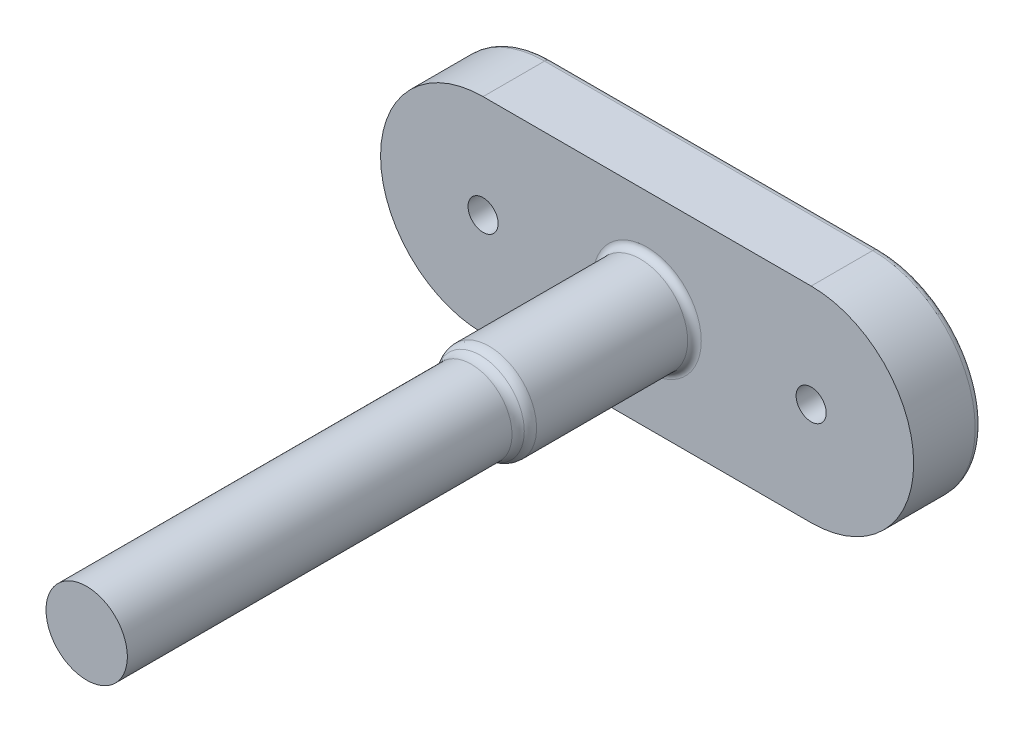
SolidWorks part; units mm, degrees
ref_plane "Front Plane" through (0, 0, 0) normal (0, 0, 1) x (1, 0, 0)
ref_plane "Top Plane" through (0, 0, 0) normal (0, 1, 0) x (1, 0, 0)
ref_plane "Right Plane" through (0, 0, 0) normal (1, 0, 0) x (0, 0, -1)
sketch "Sketch1" plane through (0, 0, 0) normal (0, 0, 1) x (1, 0, 0)
  line L0 (0, 0) -> (48, 0) construction
  line L1 (0, 15) -> (48, 15)
  line L2 (0, -15) -> (48, -15)
  arc A0 (0, 15) -> (0, -15) centre (0, 0) ccw
  arc A1 (48, -15) -> (48, 15) centre (48, 0) ccw
  circle A2 centre (0, 0) radius 2.2
  circle A3 centre (48, 0) radius 2.2
  point P3 (24, 0)
  dimension "D3" = 4.4
  dimension "D4" = 4.4
  dimension "D1" = 48
  dimension "D2" = 30
extrude "Boss-Extrude1" add sketch "Sketch1" along normal blind 10
sketch "Sketch2" plane through (0, 0, 10) normal (0, 0, 1) x (1, 0, 0)
  circle A0 centre (24, 0) radius 6.925
  dimension "D1" = 13.85
extrude "Boss-Extrude2" add sketch "Sketch2" along normal blind 24
sketch "Sketch3" plane through (0, 0, 34) normal (0, 0, 1) x (1, 0, 0)
  circle A0 centre (24, 0) radius 5.95
  dimension "D1" = 11.9
extrude "Boss-Extrude3" add sketch "Sketch3" along normal blind 58
fillet "Fillet1" radius 2 1 edges at (29.95, 0, 34)
fillet "Fillet2" radius 2 1 edges at (30.925, 0, 34)
fillet "Fillet3" radius 1 1 edges at (30.925, 0, 10)
fillet "Fillet4" radius 1 4 edges at (63, 0, 0) (24, -15, 0) (-15, 0, 0) (24, 15, 0)
